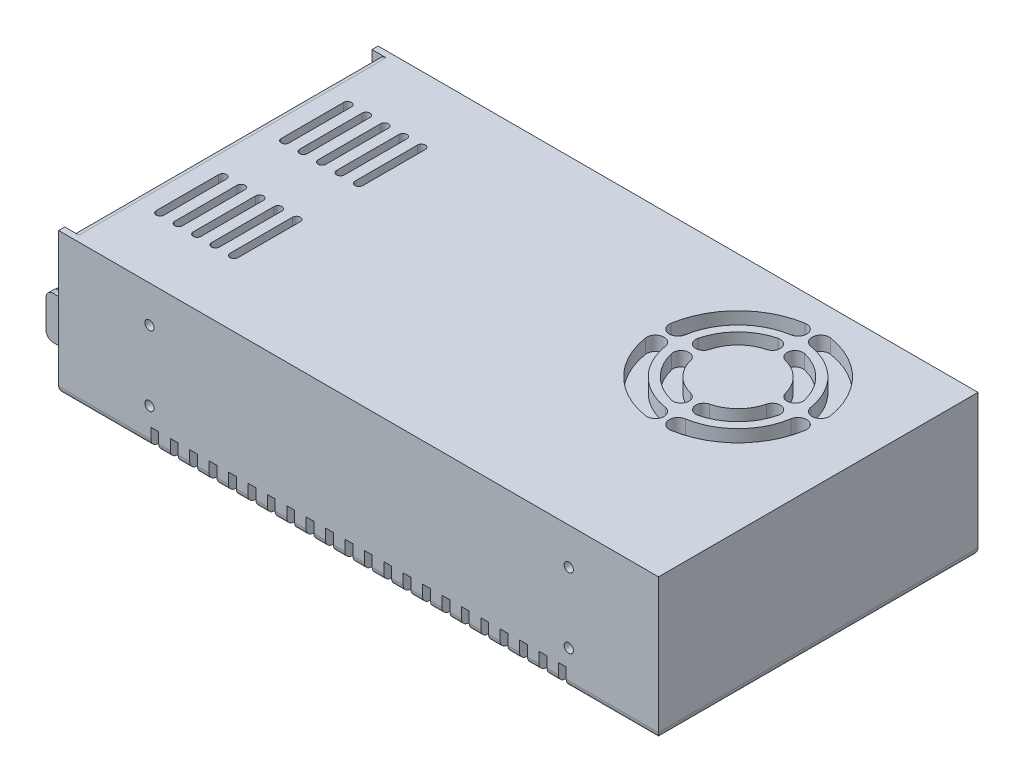
SolidWorks part; units mm, degrees
ref_plane "Front Plane" through (0, 0, 0) normal (0, 0, 1) x (1, 0, 0)
ref_plane "Top Plane" through (0, 0, 0) normal (0, 1, 0) x (1, 0, 0)
ref_plane "Right Plane" through (0, 0, 0) normal (1, 0, 0) x (0, 0, -1)
sketch "Sketch1" plane through (0, 0, 0) normal (0, 1, 0) x (1, 0, 0)
  line L1 (-107.315, -57.15) -> (107.315, -57.15)
  line L2 (-107.315, -57.15) -> (-107.315, 57.15)
  line L3 (-107.315, 57.15) -> (107.315, 57.15)
  line L4 (107.315, -57.15) -> (107.315, 57.15)
  line L5 (-107.315, -57.15) -> (107.315, 57.15) construction
  line L6 (-107.315, 57.15) -> (107.315, -57.15) construction
  point P0 (0, 0)
  dimension "D1" = 114.3
  dimension "D2" = 214.63
extrude "Boss-Extrude1" add sketch "Sketch1" along normal blind 50.8
sketch "Sketch2" plane through (0, 50.8, 0) normal (0, 1, 0) x (1, 0, 0)
  line L0 (-107.315, 57.15) -> (-107.315, -57.15) construction
  line L1 (-107.315, 54.9656) -> (-104.775, 54.9656)
  line L2 (-107.315, 54.9656) -> (-107.315, -54.9656)
  line L3 (-107.315, -54.9656) -> (-104.775, -54.9656)
  line L4 (-104.775, 54.9656) -> (-104.775, -54.9656)
  line L5 (-107.315, -57.15) -> (107.315, -57.15) construction
  line L6 (107.315, 57.15) -> (-107.315, 57.15) construction
  dimension "D1" = 2.1844
  dimension "D2" = 2.1844
  dimension "D3" = 2.54
extrude "Cut-Extrude1" cut sketch "Sketch2" against normal blind 41.91
sketch "Sketch3" plane through (-104.775, 0, 0) normal (-1, 0, 0) x (0, 0, 1)
  line L1 (-38.1508, 24.4602) -> (51.2572, 24.4602)
  line L2 (-38.1508, 24.4602) -> (-38.1508, 9.2202)
  line L3 (-38.1508, 9.2202) -> (51.2572, 9.2202)
  line L4 (51.2572, 24.4602) -> (51.2572, 9.2202)
  line L7 (-57.15, 0) -> (57.15, 0) construction
  line L8 (57.15, 50.8) -> (57.15, 0) construction
  dimension "D1" = 9.2202
  dimension "D2" = 5.8928
  dimension "D3" = 15.24
  dimension "D4" = 89.408
extrude "Boss-Extrude2" add sketch "Sketch3" along normal blind 12.7
sketch "Sketch4" plane through (-104.775, 0, 0) normal (-1, 0, 0) x (0, 0, 1)
  line L0 (-54.9656, 8.89) -> (-54.9656, 50.8) construction
  line L1 (-38.1508, 9.2202) -> (-54.9656, 9.2202)
  line L2 (51.2572, 9.2202) -> (51.2572, 24.4602)
  line L3 (51.2572, 24.4602) -> (-38.1508, 24.4602)
  line L4 (-54.9656, 9.2202) -> (-54.9656, 27.0002)
  line L5 (-54.9656, 27.0002) -> (54.9656, 27.0002)
  line L6 (54.9656, 8.89) -> (54.9656, 50.8) construction
  line L7 (54.9656, 27.0002) -> (54.9656, 9.2202)
  line L8 (54.9656, 9.2202) -> (51.2572, 9.2202)
  line L9 (-38.1508, 24.4602) -> (-38.1508, 9.2202)
  dimension "D1" = 17.78
extrude "Cut-Extrude3" cut sketch "Sketch4" against normal blind 25.4 contours L5 L7 L8 L2 L3 L9 L1 L4
sketch "Sketch5" plane through (0, 9.2202, 0) normal (0, 1, 0) x (1, 0, 0)
  line L0 (-104.775, 38.1508) -> (-104.775, 54.9656) construction
  line L1 (-103.505, 47.8536) -> (-97.155, 47.8536)
  line L2 (-103.505, 47.8536) -> (-103.505, 38.9636)
  line L3 (-103.505, 38.9636) -> (-97.155, 38.9636)
  line L4 (-97.155, 47.8536) -> (-97.155, 38.9636)
  dimension "D1" = 6.35
  dimension "D2" = 1.27
  dimension "D3" = 8.89
  dimension "D4" = 7.112
extrude "Boss-Extrude3" add sketch "Sketch5" along normal blind 8.89
sketch "Sketch6" plane through (0, 24.4602, 0) normal (0, 1, 0) x (1, 0, 0)
  line L0 (-117.475, -51.2572) -> (-117.475, 38.1508) construction
  line L1 (-117.475, 36.1188) -> (-109.347, 36.1188)
  line L2 (-117.475, 36.1188) -> (-117.475, 27.9908)
  line L3 (-117.475, 27.9908) -> (-109.347, 27.9908)
  line L4 (-109.347, 36.1188) -> (-109.347, 27.9908)
  line L5 (-117.475, 38.1508) -> (-79.375, 38.1508) construction
  line L6 (-117.475, 26.4668) -> (-109.347, 26.4668)
  line L7 (-117.475, 26.4668) -> (-117.475, 18.3388)
  line L8 (-117.475, 18.3388) -> (-109.347, 18.3388)
  line L9 (-109.347, 26.4668) -> (-109.347, 18.3388)
  line L10 (-117.475, 16.8148) -> (-109.347, 16.8148)
  line L11 (-117.475, 16.8148) -> (-117.475, 8.6868)
  line L12 (-117.475, 8.6868) -> (-109.347, 8.6868)
  line L13 (-109.347, 16.8148) -> (-109.347, 8.6868)
  line L14 (-117.475, 7.1628) -> (-109.347, 7.1628)
  line L15 (-117.475, 7.1628) -> (-117.475, -0.9652)
  line L16 (-117.475, -0.9652) -> (-109.347, -0.9652)
  line L17 (-109.347, 7.1628) -> (-109.347, -0.9652)
  line L18 (-117.475, -2.4892) -> (-109.347, -2.4892)
  line L19 (-117.475, -2.4892) -> (-117.475, -10.6172)
  line L20 (-117.475, -10.6172) -> (-109.347, -10.6172)
  line L21 (-109.347, -2.4892) -> (-109.347, -10.6172)
  line L22 (-117.475, -12.1412) -> (-109.347, -12.1412)
  line L23 (-117.475, -12.1412) -> (-117.475, -20.2692)
  line L24 (-117.475, -20.2692) -> (-109.347, -20.2692)
  line L25 (-109.347, -12.1412) -> (-109.347, -20.2692)
  line L26 (-117.475, -21.7932) -> (-109.347, -21.7932)
  line L27 (-117.475, -21.7932) -> (-117.475, -29.9212)
  line L28 (-117.475, -29.9212) -> (-109.347, -29.9212)
  line L29 (-109.347, -21.7932) -> (-109.347, -29.9212)
  line L30 (-117.475, -31.4452) -> (-109.347, -31.4452)
  line L31 (-117.475, -31.4452) -> (-117.475, -39.5732)
  line L32 (-117.475, -39.5732) -> (-109.347, -39.5732)
  line L33 (-109.347, -31.4452) -> (-109.347, -39.5732)
  line L35 (-117.475, -41.0972) -> (-109.347, -41.0972)
  line L36 (-117.475, -41.0972) -> (-117.475, -49.2252)
  line L37 (-117.475, -49.2252) -> (-109.347, -49.2252)
  line L38 (-109.347, -41.0972) -> (-109.347, -49.2252)
  line L39 (-117.475, -51.2572) -> (-79.375, -51.2572) construction
  dimension "D1" = 2.032
  dimension "D2" = 8.128
  dimension "D3" = 8.128
  dimension "D5" = 2.032
  dimension "D4" = 9
extrude "Cut-Extrude4" cut sketch "Sketch6" against normal through all
sketch "Sketch7" plane through (-103.505, 0, 0) normal (-1, 0, 0) x (0, 0, 1)
  line L0 (-38.9636, 18.1102) -> (-38.9636, 9.2202) construction
  line L1 (-47.8536, 18.1102) -> (-38.9636, 18.1102) construction
  circle A0 centre (-43.4086, 13.6652) radius 1.905
  point P4 (-38.9636, 13.6652)
  point P7 (-43.4086, 18.1102)
  dimension "D1" = 3.81
extrude "Cut-Extrude5" cut sketch "Sketch7" against normal blind 0.254
sketch "Sketch8" plane through (-109.347, 0, 0) normal (-1, 0, 0) x (0, 0, 1)
  line L0 (-27.9908, 9.2202) -> (-36.1188, 9.2202) construction
  line L2 (49.2252, 24.4602) -> (41.0972, 24.4602) construction
  circle A0 centre (-32.0548, 16.8402) radius 1.905
  circle A1 centre (-22.4028, 16.8402) radius 1.905
  circle A2 centre (-12.7508, 16.8402) radius 1.905
  circle A3 centre (-3.0988, 16.8402) radius 1.905
  circle A4 centre (6.5532, 16.8402) radius 1.905
  circle A5 centre (16.2052, 16.8402) radius 1.905
  circle A6 centre (25.8572, 16.8402) radius 1.905
  circle A7 centre (35.5092, 16.8402) radius 1.905
  circle A8 centre (45.1612, 16.8402) radius 1.905
  point P4 (-32.0548, 9.2202)
  point P23 (45.1612, 24.4602)
  dimension "D1" = 3.81
  dimension "D2" = 7.62
  dimension "D3" = 9
extrude "Boss-Extrude4" add sketch "Sketch8" along normal blind 2.54
sketch "Sketch9" plane through (-111.887, 0, 0) normal (-1, 0, 0) x (0, 0, 1)
  circle A0 centre (-32.0548, 16.8402) radius 3.81
  circle A1 centre (-22.4028, 16.8402) radius 3.81
  circle A2 centre (-12.7508, 16.8402) radius 3.81
  circle A3 centre (-3.0988, 16.8402) radius 3.81
  circle A4 centre (6.5532, 16.8402) radius 3.81
  circle A5 centre (16.2052, 16.8402) radius 3.81
  circle A6 centre (25.8572, 16.8402) radius 3.81
  circle A7 centre (35.5092, 16.8402) radius 3.81
  circle A12 centre (45.1612, 16.8402) radius 3.81
  dimension "D1" = 7.62
extrude "Boss-Extrude5" add sketch "Sketch9" along normal blind 3.81
fillet "Fillet1" radius 1.27 9 edges at (-115.697, 16.8402, -28.2448) (-115.697, 16.8402, 10.3632) (-115.697, 16.8402, 48.9712) (-115.697, 16.8402, 39.3192) (-115.697, 16.8402, 29.6672) (-115.697, 16.8402, 20.0152) (-115.697, 16.8402, 0.7112) (-115.697, 16.8402, -8.9408) (-115.697, 16.8402, -18.5928)
sketch "Sketch10" plane through (0, 50.8, 0) normal (0, 1, 0) x (1, 0, 0)
  line L0 (107.315, 57.15) -> (-107.315, 57.15) construction
  line L1 (107.315, -57.15) -> (107.315, 57.15) construction
  line L2 (85.086, 23.114) -> (85.086, 14.986) construction
  line L3 (59.563, 48.006) -> (59.563, -9.906) construction
  line L4 (85.086, 19.05) -> (59.563, 19.05) construction
  line L5 (63.627, 44.573) -> (55.499, 44.573) construction
  line L6 (34.04, 23.114) -> (34.04, 14.986) construction
  arc A0 (73.1195, 22.4239) -> (62.9369, 32.6065) centre (59.563, 19.05) ccw
  arc A1 (78.6653, 23.8041) -> (64.3171, 38.1523) centre (59.563, 19.05) ccw
  arc A2 (82.0132, 22.6247) -> (63.1377, 41.5002) centre (59.563, 19.05) ccw
  arc A3 (88.1588, 23.6033) -> (64.1163, 47.6458) centre (59.563, 19.05) ccw
  arc A4 (82.0132, 22.6247) -> (88.1588, 23.6033) centre (85.086, 23.114) ccw
  arc A5 (64.1163, 47.6458) -> (63.1377, 41.5002) centre (63.627, 44.573) ccw
  arc A6 (64.3171, 38.1523) -> (62.9369, 32.6065) centre (63.627, 35.3794) ccw
  arc A7 (73.1195, 15.6761) -> (78.6653, 14.2959) centre (75.8924, 14.986) cw
  arc A8 (73.1195, 22.4239) -> (78.6653, 23.8041) centre (75.8924, 23.114) ccw
  arc A9 (64.3171, -0.0523) -> (62.9369, 5.4935) centre (63.627, 2.7206) cw
  arc A10 (64.1163, -9.5458) -> (63.1377, -3.4002) centre (63.627, -6.473) cw
  arc A11 (82.0132, 15.4753) -> (88.1588, 14.4967) centre (85.086, 14.986) cw
  arc A12 (88.1588, 14.4967) -> (64.1163, -9.5458) centre (59.563, 19.05) cw
  arc A13 (82.0132, 15.4753) -> (63.1377, -3.4002) centre (59.563, 19.05) cw
  arc A14 (78.6653, 14.2959) -> (64.3171, -0.0523) centre (59.563, 19.05) cw
  arc A15 (73.1195, 15.6761) -> (62.9369, 5.4935) centre (59.563, 19.05) cw
  arc A16 (46.0065, 15.6761) -> (56.1891, 5.4935) centre (59.563, 19.05) ccw
  arc A17 (40.4607, 14.2959) -> (54.8089, -0.0523) centre (59.563, 19.05) ccw
  arc A18 (37.1128, 15.4753) -> (55.9883, -3.4002) centre (59.563, 19.05) ccw
  arc A19 (30.9672, 14.4967) -> (55.0097, -9.5458) centre (59.563, 19.05) ccw
  arc A20 (37.1128, 15.4753) -> (30.9672, 14.4967) centre (34.04, 14.986) ccw
  arc A21 (55.0097, -9.5458) -> (55.9883, -3.4002) centre (55.499, -6.473) ccw
  arc A22 (54.8089, -0.0523) -> (56.1891, 5.4935) centre (55.499, 2.7206) ccw
  arc A23 (46.0065, 22.4239) -> (40.4607, 23.8041) centre (43.2336, 23.114) cw
  arc A24 (46.0065, 15.6761) -> (40.4607, 14.2959) centre (43.2336, 14.986) ccw
  arc A25 (54.8089, 38.1523) -> (56.1891, 32.6065) centre (55.499, 35.3794) cw
  arc A26 (55.0097, 47.6458) -> (55.9883, 41.5002) centre (55.499, 44.573) cw
  arc A27 (37.1128, 22.6247) -> (30.9672, 23.6033) centre (34.04, 23.114) cw
  arc A28 (30.9672, 23.6033) -> (55.0097, 47.6458) centre (59.563, 19.05) cw
  arc A29 (37.1128, 22.6247) -> (55.9883, 41.5002) centre (59.563, 19.05) cw
  arc A30 (40.4607, 23.8041) -> (54.8089, 38.1523) centre (59.563, 19.05) cw
  arc A31 (46.0065, 22.4239) -> (56.1891, 32.6065) centre (59.563, 19.05) cw
  point P6 (59.563, 44.573)
  dimension "D1" = 38.1
  dimension "D3" = 27.94
  dimension "D4" = 39.37
  dimension "D5" = 3.048
  dimension "D6" = 57.912
  dimension "D7" = 8.128
  dimension "D2" = 47.752
extrude "Cut-Extrude6" cut sketch "Sketch10" against normal blind 5.08
sketch "Sketch11" plane through (0, 50.8, 0) normal (0, 1, 0) x (1, 0, 0)
  line L0 (-94.615, 33.528) -> (-94.615, 11.176) construction
  line L1 (-93.218, 33.528) -> (-93.218, 11.176)
  line L2 (-96.012, 33.528) -> (-96.012, 11.176)
  line L3 (-94.615, -11.176) -> (-94.615, -33.528) construction
  line L4 (-93.218, -11.176) -> (-93.218, -33.528)
  line L5 (-96.012, -11.176) -> (-96.012, -33.528)
  line L6 (-104.775, 0) -> (107.315, 0) construction
  line L7 (-104.775, -54.9656) -> (-104.775, 54.9656) construction
  line L8 (107.315, -57.15) -> (107.315, 57.15) construction
  line L9 (-94.615, 11.176) -> (-94.615, -11.176) construction
  line L10 (-88.011, 11.176) -> (-88.011, -11.176) construction
  line L11 (-88.011, 33.528) -> (-88.011, 11.176) construction
  line L12 (-86.614, 33.528) -> (-86.614, 11.176)
  line L13 (-89.408, 33.528) -> (-89.408, 11.176)
  line L14 (-88.011, -11.176) -> (-88.011, -33.528) construction
  line L15 (-86.614, -11.176) -> (-86.614, -33.528)
  line L16 (-89.408, -11.176) -> (-89.408, -33.528)
  line L17 (-81.407, 11.176) -> (-81.407, -11.176) construction
  line L18 (-81.407, 33.528) -> (-81.407, 11.176) construction
  line L19 (-80.01, 33.528) -> (-80.01, 11.176)
  line L20 (-82.804, 33.528) -> (-82.804, 11.176)
  line L21 (-81.407, -11.176) -> (-81.407, -33.528) construction
  line L22 (-80.01, -11.176) -> (-80.01, -33.528)
  line L23 (-82.804, -11.176) -> (-82.804, -33.528)
  line L24 (-74.803, 11.176) -> (-74.803, -11.176) construction
  line L25 (-74.803, 33.528) -> (-74.803, 11.176) construction
  line L26 (-73.406, 33.528) -> (-73.406, 11.176)
  line L27 (-76.2, 33.528) -> (-76.2, 11.176)
  line L28 (-74.803, -11.176) -> (-74.803, -33.528) construction
  line L29 (-73.406, -11.176) -> (-73.406, -33.528)
  line L30 (-76.2, -11.176) -> (-76.2, -33.528)
  line L31 (-68.199, 11.176) -> (-68.199, -11.176) construction
  line L32 (-68.199, 33.528) -> (-68.199, 11.176) construction
  line L33 (-66.802, 33.528) -> (-66.802, 11.176)
  line L34 (-69.596, 33.528) -> (-69.596, 11.176)
  line L35 (-68.199, -11.176) -> (-68.199, -33.528) construction
  line L36 (-66.802, -11.176) -> (-66.802, -33.528)
  line L37 (-69.596, -11.176) -> (-69.596, -33.528)
  arc A0 (-93.218, 33.528) -> (-96.012, 33.528) centre (-94.615, 33.528) ccw
  arc A1 (-96.012, 11.176) -> (-93.218, 11.176) centre (-94.615, 11.176) ccw
  arc A2 (-93.218, -11.176) -> (-96.012, -11.176) centre (-94.615, -11.176) ccw
  arc A3 (-96.012, -33.528) -> (-93.218, -33.528) centre (-94.615, -33.528) ccw
  arc A4 (-86.614, 33.528) -> (-89.408, 33.528) centre (-88.011, 33.528) ccw
  arc A5 (-89.408, 11.176) -> (-86.614, 11.176) centre (-88.011, 11.176) ccw
  arc A6 (-86.614, -11.176) -> (-89.408, -11.176) centre (-88.011, -11.176) ccw
  arc A7 (-89.408, -33.528) -> (-86.614, -33.528) centre (-88.011, -33.528) ccw
  arc A8 (-80.01, 33.528) -> (-82.804, 33.528) centre (-81.407, 33.528) ccw
  arc A9 (-82.804, 11.176) -> (-80.01, 11.176) centre (-81.407, 11.176) ccw
  arc A10 (-80.01, -11.176) -> (-82.804, -11.176) centre (-81.407, -11.176) ccw
  arc A11 (-82.804, -33.528) -> (-80.01, -33.528) centre (-81.407, -33.528) ccw
  arc A12 (-73.406, 33.528) -> (-76.2, 33.528) centre (-74.803, 33.528) ccw
  arc A13 (-76.2, 11.176) -> (-73.406, 11.176) centre (-74.803, 11.176) ccw
  arc A14 (-73.406, -11.176) -> (-76.2, -11.176) centre (-74.803, -11.176) ccw
  arc A15 (-76.2, -33.528) -> (-73.406, -33.528) centre (-74.803, -33.528) ccw
  arc A16 (-66.802, 33.528) -> (-69.596, 33.528) centre (-68.199, 33.528) ccw
  arc A17 (-69.596, 11.176) -> (-66.802, 11.176) centre (-68.199, 11.176) ccw
  arc A18 (-66.802, -11.176) -> (-69.596, -11.176) centre (-68.199, -11.176) ccw
  arc A19 (-69.596, -33.528) -> (-66.802, -33.528) centre (-68.199, -33.528) ccw
  point P2 (-94.615, 22.352)
  point P7 (-94.615, -22.352)
  point P22 (-94.615, 0)
  point P26 (-88.011, 22.352)
  point P31 (-88.011, -22.352)
  point P42 (-81.407, 22.352)
  point P47 (-81.407, -22.352)
  point P58 (-74.803, 22.352)
  point P63 (-74.803, -22.352)
  point P74 (-68.199, 22.352)
  point P79 (-68.199, -22.352)
  dimension "D1" = 22.352
  dimension "D2" = 22.352
  dimension "D3" = 10.16
  dimension "D4" = 2.794
  dimension "D6" = 6.604
  dimension "D5" = 5
extrude "Cut-Extrude7" cut sketch "Sketch11" against normal blind 5.08
fillet "Fillet2" radius 2.54 5 edges at (0, 0, -57.15) (-107.315, 0, 0) (0, 0, 57.15) (107.315, 0, 0) (-104.775, 50.8, 0)
sketch "Sketch12" plane through (0, 0, 0) normal (0, -1, 0) x (1, 0, 0)
  line L0 (72.898, 40.132) -> (72.898, 57.15) construction
  line L1 (-107.315, 57.15) -> (107.315, 57.15) construction
  line L2 (71.501, 40.132) -> (71.501, 57.15)
  line L3 (74.295, 40.132) -> (74.295, 57.15)
  line L4 (107.315, 57.15) -> (107.315, -57.15) construction
  line L5 (65.9553, 40.132) -> (65.9553, 57.15) construction
  line L6 (64.5583, 40.132) -> (64.5583, 57.15)
  line L7 (67.3523, 40.132) -> (67.3523, 57.15)
  line L8 (59.0127, 40.132) -> (59.0127, 57.15) construction
  line L9 (57.6157, 40.132) -> (57.6157, 57.15)
  line L10 (60.4097, 40.132) -> (60.4097, 57.15)
  line L11 (52.07, 40.132) -> (52.07, 57.15) construction
  line L12 (50.673, 40.132) -> (50.673, 57.15)
  line L13 (53.467, 40.132) -> (53.467, 57.15)
  line L14 (45.1273, 40.132) -> (45.1273, 57.15) construction
  line L15 (43.7303, 40.132) -> (43.7303, 57.15)
  line L16 (46.5243, 40.132) -> (46.5243, 57.15)
  line L17 (38.1847, 40.132) -> (38.1847, 57.15) construction
  line L18 (36.7877, 40.132) -> (36.7877, 57.15)
  line L19 (39.5817, 40.132) -> (39.5817, 57.15)
  line L20 (31.242, 40.132) -> (31.242, 57.15) construction
  line L21 (29.845, 40.132) -> (29.845, 57.15)
  line L22 (32.639, 40.132) -> (32.639, 57.15)
  line L23 (24.2993, 40.132) -> (24.2993, 57.15) construction
  line L24 (22.9023, 40.132) -> (22.9023, 57.15)
  line L25 (25.6963, 40.132) -> (25.6963, 57.15)
  line L26 (17.3567, 40.132) -> (17.3567, 57.15) construction
  line L27 (15.9597, 40.132) -> (15.9597, 57.15)
  line L28 (18.7537, 40.132) -> (18.7537, 57.15)
  line L29 (10.414, 40.132) -> (10.414, 57.15) construction
  line L30 (9.017, 40.132) -> (9.017, 57.15)
  line L31 (11.811, 40.132) -> (11.811, 57.15)
  line L32 (3.4713, 40.132) -> (3.4713, 57.15) construction
  line L33 (2.0743, 40.132) -> (2.0743, 57.15)
  line L34 (4.8683, 40.132) -> (4.8683, 57.15)
  line L35 (-3.4713, 40.132) -> (-3.4713, 57.15) construction
  line L36 (-4.8683, 40.132) -> (-4.8683, 57.15)
  line L37 (-2.0743, 40.132) -> (-2.0743, 57.15)
  line L38 (-10.414, 40.132) -> (-10.414, 57.15) construction
  line L39 (-11.811, 40.132) -> (-11.811, 57.15)
  line L40 (-9.017, 40.132) -> (-9.017, 57.15)
  line L41 (-17.3567, 40.132) -> (-17.3567, 57.15) construction
  line L42 (-18.7537, 40.132) -> (-18.7537, 57.15)
  line L43 (-15.9597, 40.132) -> (-15.9597, 57.15)
  line L44 (-24.2993, 40.132) -> (-24.2993, 57.15) construction
  line L45 (-25.6963, 40.132) -> (-25.6963, 57.15)
  line L46 (-22.9023, 40.132) -> (-22.9023, 57.15)
  line L47 (-31.242, 40.132) -> (-31.242, 57.15) construction
  line L48 (-32.639, 40.132) -> (-32.639, 57.15)
  line L49 (-29.845, 40.132) -> (-29.845, 57.15)
  line L50 (-38.1847, 40.132) -> (-38.1847, 57.15) construction
  line L51 (-39.5817, 40.132) -> (-39.5817, 57.15)
  line L52 (-36.7877, 40.132) -> (-36.7877, 57.15)
  line L53 (-45.1273, 40.132) -> (-45.1273, 57.15) construction
  line L54 (-46.5243, 40.132) -> (-46.5243, 57.15)
  line L55 (-43.7303, 40.132) -> (-43.7303, 57.15)
  line L56 (-52.07, 40.132) -> (-52.07, 57.15) construction
  line L57 (-53.467, 40.132) -> (-53.467, 57.15)
  line L58 (-50.673, 40.132) -> (-50.673, 57.15)
  line L59 (-59.0127, 40.132) -> (-59.0127, 57.15) construction
  line L60 (-60.4097, 40.132) -> (-60.4097, 57.15)
  line L61 (-57.6157, 40.132) -> (-57.6157, 57.15)
  line L62 (-65.9553, 40.132) -> (-65.9553, 57.15) construction
  line L63 (-67.3523, 40.132) -> (-67.3523, 57.15)
  line L64 (-64.5583, 40.132) -> (-64.5583, 57.15)
  line L65 (-72.898, 40.132) -> (-72.898, 57.15) construction
  line L66 (-74.295, 40.132) -> (-74.295, 57.15)
  line L67 (-71.501, 40.132) -> (-71.501, 57.15)
  line L68 (-107.315, -57.15) -> (-107.315, 57.15) construction
  arc A0 (71.501, 40.132) -> (74.295, 40.132) centre (72.898, 40.132) ccw
  arc A1 (74.295, 57.15) -> (71.501, 57.15) centre (72.898, 57.15) ccw
  arc A2 (64.5583, 40.132) -> (67.3523, 40.132) centre (65.9553, 40.132) ccw
  arc A3 (67.3523, 57.15) -> (64.5583, 57.15) centre (65.9553, 57.15) ccw
  arc A4 (57.6157, 40.132) -> (60.4097, 40.132) centre (59.0127, 40.132) ccw
  arc A5 (60.4097, 57.15) -> (57.6157, 57.15) centre (59.0127, 57.15) ccw
  arc A6 (50.673, 40.132) -> (53.467, 40.132) centre (52.07, 40.132) ccw
  arc A7 (53.467, 57.15) -> (50.673, 57.15) centre (52.07, 57.15) ccw
  arc A8 (43.7303, 40.132) -> (46.5243, 40.132) centre (45.1273, 40.132) ccw
  arc A9 (46.5243, 57.15) -> (43.7303, 57.15) centre (45.1273, 57.15) ccw
  arc A10 (36.7877, 40.132) -> (39.5817, 40.132) centre (38.1847, 40.132) ccw
  arc A11 (39.5817, 57.15) -> (36.7877, 57.15) centre (38.1847, 57.15) ccw
  arc A12 (29.845, 40.132) -> (32.639, 40.132) centre (31.242, 40.132) ccw
  arc A13 (32.639, 57.15) -> (29.845, 57.15) centre (31.242, 57.15) ccw
  arc A14 (22.9023, 40.132) -> (25.6963, 40.132) centre (24.2993, 40.132) ccw
  arc A15 (25.6963, 57.15) -> (22.9023, 57.15) centre (24.2993, 57.15) ccw
  arc A16 (15.9597, 40.132) -> (18.7537, 40.132) centre (17.3567, 40.132) ccw
  arc A17 (18.7537, 57.15) -> (15.9597, 57.15) centre (17.3567, 57.15) ccw
  arc A18 (9.017, 40.132) -> (11.811, 40.132) centre (10.414, 40.132) ccw
  arc A19 (11.811, 57.15) -> (9.017, 57.15) centre (10.414, 57.15) ccw
  arc A20 (2.0743, 40.132) -> (4.8683, 40.132) centre (3.4713, 40.132) ccw
  arc A21 (4.8683, 57.15) -> (2.0743, 57.15) centre (3.4713, 57.15) ccw
  arc A22 (-4.8683, 40.132) -> (-2.0743, 40.132) centre (-3.4713, 40.132) ccw
  arc A23 (-2.0743, 57.15) -> (-4.8683, 57.15) centre (-3.4713, 57.15) ccw
  arc A24 (-11.811, 40.132) -> (-9.017, 40.132) centre (-10.414, 40.132) ccw
  arc A25 (-9.017, 57.15) -> (-11.811, 57.15) centre (-10.414, 57.15) ccw
  arc A26 (-18.7537, 40.132) -> (-15.9597, 40.132) centre (-17.3567, 40.132) ccw
  arc A27 (-15.9597, 57.15) -> (-18.7537, 57.15) centre (-17.3567, 57.15) ccw
  arc A28 (-25.6963, 40.132) -> (-22.9023, 40.132) centre (-24.2993, 40.132) ccw
  arc A29 (-22.9023, 57.15) -> (-25.6963, 57.15) centre (-24.2993, 57.15) ccw
  arc A30 (-32.639, 40.132) -> (-29.845, 40.132) centre (-31.242, 40.132) ccw
  arc A31 (-29.845, 57.15) -> (-32.639, 57.15) centre (-31.242, 57.15) ccw
  arc A32 (-39.5817, 40.132) -> (-36.7877, 40.132) centre (-38.1847, 40.132) ccw
  arc A33 (-36.7877, 57.15) -> (-39.5817, 57.15) centre (-38.1847, 57.15) ccw
  arc A34 (-46.5243, 40.132) -> (-43.7303, 40.132) centre (-45.1273, 40.132) ccw
  arc A35 (-43.7303, 57.15) -> (-46.5243, 57.15) centre (-45.1273, 57.15) ccw
  arc A36 (-53.467, 40.132) -> (-50.673, 40.132) centre (-52.07, 40.132) ccw
  arc A37 (-50.673, 57.15) -> (-53.467, 57.15) centre (-52.07, 57.15) ccw
  arc A38 (-60.4097, 40.132) -> (-57.6157, 40.132) centre (-59.0127, 40.132) ccw
  arc A39 (-57.6157, 57.15) -> (-60.4097, 57.15) centre (-59.0127, 57.15) ccw
  arc A40 (-67.3523, 40.132) -> (-64.5583, 40.132) centre (-65.9553, 40.132) ccw
  arc A41 (-64.5583, 57.15) -> (-67.3523, 57.15) centre (-65.9553, 57.15) ccw
  arc A42 (-74.295, 40.132) -> (-71.501, 40.132) centre (-72.898, 40.132) ccw
  arc A43 (-71.501, 57.15) -> (-74.295, 57.15) centre (-72.898, 57.15) ccw
  point P4 (72.898, 48.641)
  point P15 (65.9553, 48.641)
  point P22 (59.0127, 48.641)
  point P29 (52.07, 48.641)
  point P36 (45.1273, 48.641)
  point P43 (38.1847, 48.641)
  point P50 (31.242, 48.641)
  point P57 (24.2993, 48.641)
  point P64 (17.3567, 48.641)
  point P71 (10.414, 48.641)
  point P78 (3.4713, 48.641)
  point P85 (-3.4713, 48.641)
  point P92 (-10.414, 48.641)
  point P99 (-17.3567, 48.641)
  point P106 (-24.2993, 48.641)
  point P113 (-31.242, 48.641)
  point P120 (-38.1847, 48.641)
  point P127 (-45.1273, 48.641)
  point P134 (-52.07, 48.641)
  point P141 (-59.0127, 48.641)
  point P148 (-65.9553, 48.641)
  point P155 (-72.898, 48.641)
  dimension "D1" = 1.397
  dimension "D2" = 17.018
  dimension "D3" = 33.02
  dimension "D5" = 33.02
  dimension "D4" = 22
extrude "Cut-Extrude8" cut sketch "Sketch12" against normal blind 6.35
mirror "Mirror1" about plane through (0, 0, 0) normal (0, 0, 1) of "Cut-Extrude8"
sketch "Sketch13" plane through (-117.475, 0, 0) normal (-1, 0, 0) x (0, 0, 1)
  line L1 (-38.1508, 9.2202) -> (51.2572, 9.2202)
  line L2 (-38.1508, 9.2202) -> (-38.1508, 24.4602)
  line L3 (-38.1508, 24.4602) -> (51.2572, 24.4602)
  line L4 (51.2572, 9.2202) -> (51.2572, 24.4602)
extrude "Boss-Extrude6" add sketch "Sketch13" along normal blind 0.254
fillet "Fillet3" radius 2.54 2 edges at (-117.729, 9.2202, 6.5532) (-117.729, 24.4602, 6.5532)
sketch "Sketch14" plane through (-104.775, 0, 0) normal (-1, 0, 0) x (0, 0, 1)
  line L0 (-54.9656, 33.3502) -> (54.9656, 33.3502) construction
  line L1 (-54.9656, 27.0002) -> (54.9656, 27.0002) construction
  line L2 (-54.9656, 8.89) -> (-54.9656, 50.8) construction
  line L3 (54.9656, 27.0002) -> (54.9656, 48.26) construction
  text T0 "  V          +V            -V        =   N  L" font "Century Gothic" height in points 18
  text T1 "      adj                      |                  |"
  dimension "D1" = 6.35
extrude "Cut-Extrude9" cut sketch "Sketch14" against normal blind 0.254
hole_wizard "M4x0.7 Tapped Hole1" positions "Sketch16" profile "Sketch15" tap size "M4x0.7" standard "ANSI Metric"
sketch "Sketch16" plane through (0, 0, -57.15) normal (0, 0, -1) x (-1, 0, 0)
  line L0 (-107.315, 50.8) -> (-107.315, 2.54) construction
  line L1 (107.315, 50.8) -> (107.315, 2.54) construction
  line L2 (104.775, 0) -> (74.295, 0) construction
  point P0 (75.565, 12.7)
  point P2 (-75.565, 12.7)
  dimension "D1" = 31.75
  dimension "D2" = 31.75
  dimension "D3" = 12.7
sketch "Sketch15" plane through (-75.565, 12.7, -57.15) normal (1, 0, 0) x (0, 1, 0)
  line L0 (0, 0) -> (0, 10.8974)
  line L1 (0, 10.8974) -> (1.65, 9.906)
  line L2 (1.65, 9.906) -> (1.65, 0)
  line L5 (1.65, 0) -> (0, 0)
  line L10 (0, 10.8974) -> (-1.65, 9.906) construction
  line L11 (0, -6.35) -> (0, 107.95) construction
  dimension "Tap Drill Dia." = 3.3
  dimension "Tap Drill Depth" = 9.906
  dimension "Drill Angle" = 118
hole_wizard "M4x0.7 Tapped Hole2" positions "Sketch18" profile "Sketch17" tap size "M4x0.7" standard "ANSI Metric"
sketch "Sketch18" plane through (0, 0, 57.15) normal (0, 0, 1) x (1, 0, 0)
  line L0 (104.775, 0) -> (74.295, 0) construction
  line L2 (-107.315, 50.8) -> (-107.315, 2.54) construction
  line L3 (-74.295, 0) -> (-104.775, 0) construction
  point P0 (75.185, 12.7)
  point P2 (75.185, 37.7)
  point P4 (-74.815, 37.7)
  point P6 (-74.815, 12.7)
  dimension "D1" = 12.7
  dimension "D2" = 150
  dimension "D3" = 25
  dimension "D4" = 32.5
  dimension "D5" = 12.7
sketch "Sketch17" plane through (75.185, 12.7, 57.15) normal (1, 0, 0) x (0, -1, 0)
  line L0 (0, 0) -> (0, 10.8974)
  line L1 (0, 10.8974) -> (1.65, 9.906)
  line L2 (1.65, 9.906) -> (1.65, 0)
  line L5 (1.65, 0) -> (0, 0)
  line L10 (0, 10.8974) -> (-1.65, 9.906) construction
  line L11 (0, -6.35) -> (0, 107.95) construction
  dimension "Tap Drill Dia." = 3.3
  dimension "Tap Drill Depth" = 9.906
  dimension "Drill Angle" = 118
hole_wizard "M4x0.7 Tapped Hole3" positions "Sketch20" profile "Sketch19" tap size "M4x0.7" standard "ANSI Metric"
sketch "Sketch20" plane through (0, 0, 0) normal (0, -1, 0) x (-1, 0, 0)
  line L4 (-107.315, 57.15) -> (-74.295, 57.15) construction
  line L5 (107.315, 57.15) -> (107.315, -57.15) construction
  point P0 (-75.185, -25.35)
  point P2 (-75.185, 24.65)
  point P4 (74.815, 24.65)
  point P6 (74.815, -25.35)
  dimension "D1" = 50
  dimension "D2" = 150
  dimension "D3" = 32.5
  dimension "D4" = 32.5
sketch "Sketch19" plane through (75.185, 0, 25.35) normal (1, 0, 0) x (0, 0, -1)
  line L0 (0, 0) -> (0, 10.8974)
  line L1 (0, 10.8974) -> (1.65, 9.906)
  line L2 (1.65, 9.906) -> (1.65, 0)
  line L5 (1.65, 0) -> (0, 0)
  line L10 (0, 10.8974) -> (-1.65, 9.906) construction
  line L11 (0, -6.35) -> (0, 107.95) construction
  dimension "Tap Drill Dia." = 3.3
  dimension "Tap Drill Depth" = 9.906
  dimension "Drill Angle" = 118
sketch "Sketch21" plane through (-107.315, 0, 0) normal (-1, 0, 0) x (0, 0, 1)
  line L0 (57.15, 25.4) -> (57.15, 41.275)
  line L1 (57.15, 50.8) -> (57.15, 2.54) construction
  line L2 (57.15, 41.275) -> (62.15, 43.9)
  line L3 (62.15, 43.9) -> (64.3965, 43.9)
  line L4 (64.3965, 43.9) -> (64.9215, 42.9)
  line L5 (64.9215, 42.9) -> (66.4429, 42.9)
  line L6 (66.4429, 42.9) -> (67.4429, 43.9)
  line L7 (66.8571, 41.9) -> (68.15, 43.1929)
  line L8 (66.8571, 41.9) -> (64.3171, 41.9)
  line L9 (64.3171, 41.9) -> (63.7921, 42.9)
  line L10 (63.7921, 42.9) -> (62.3965, 42.9)
  line L11 (62.3965, 42.9) -> (58.15, 40.6706)
  line L12 (58.15, 40.6706) -> (58.15, 25.4)
  line L13 (58.15, 25.4) -> (57.15, 25.4)
  line L14 (68.15, 43.1929) -> (67.4429, 43.9)
  line L15 (54.9656, 50.8) -> (57.15, 50.8) construction
  dimension "D1" = 15.875
  dimension "D2" = 1
  dimension "D3" = 16.5
  dimension "D4" = 1
  dimension "D5" = 1
  dimension "D6" = 1
  dimension "D7" = 1
  dimension "D8" = 1
  dimension "D9" = 11
  dimension "D10" = 5
  dimension "D11" = 17.5
  dimension "D12" = 135
  dimension "D13" = 25.4
  dimension "D14" = 2.54
extrude "Boss-Extrude7" [suppressed] add sketch "Sketch21" against normal blind 12.7 from offset 25.4 offset against normal yes
ref_plane "Plane1" through (0, 0, 0) normal (-1, 0, 0) x (0, 0, 1)
mirror "Mirror6" [suppressed] about plane through (0, 0, 0) normal (-1, 0, 0)
mirror "Mirror2" [suppressed]
